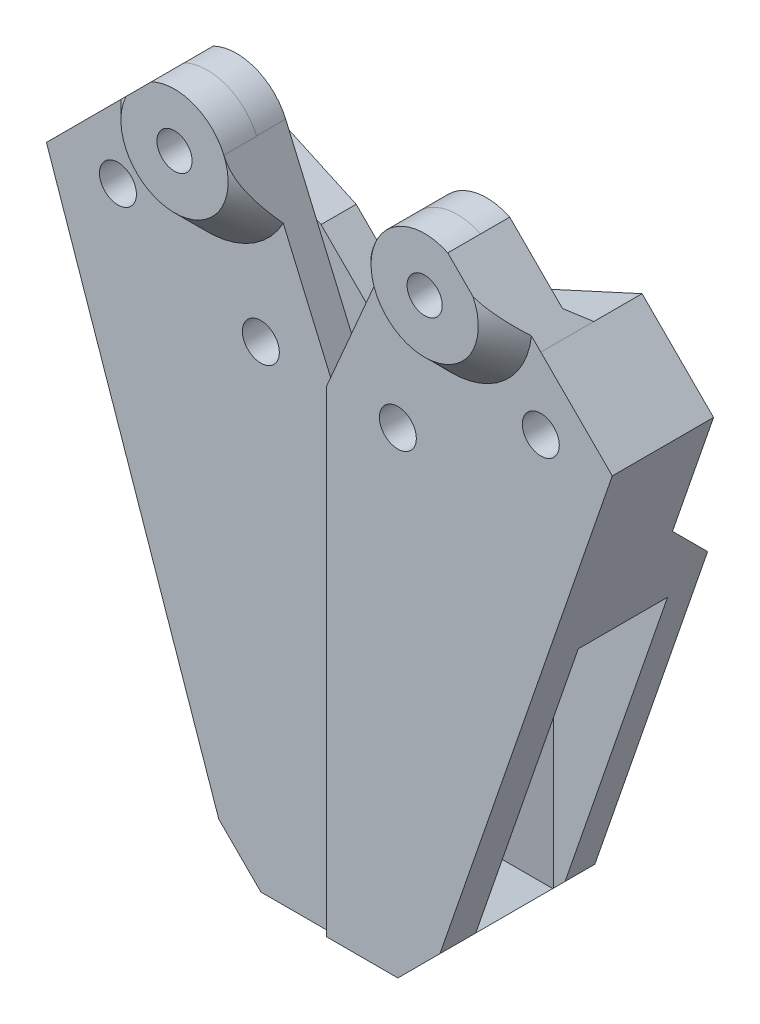
SolidWorks part; units mm, degrees
material "ABS"
ref_plane "Płaszczyzna przednia" through (0, 0, 0) normal (0, 0, 1) x (1, 0, 0)
ref_plane "Płaszczyzna górna" through (0, 0, 0) normal (0, 1, 0) x (1, 0, 0)
ref_plane "Płaszczyzna prawa" through (0, 0, 0) normal (1, 0, 0) x (0, 0, -1)
sketch "Szkic1" plane through (0, 0, 0) normal (0, 0, 1) x (1, 0, 0)
  line L0 (-24, 11) -> (-24, 23)
  line L1 (-24, 11) -> (-36, 11)
  line L2 (-24, 23) -> (-36, 11)
  line L3 (0, 0) -> (0, 12)
  line L4 (0, 12) -> (-24, 23)
  line L5 (0, 0) -> (12, 0)
  line L6 (0, 12) -> (12, 0)
  line L7 (0, 0) -> (0, -80)
  line L8 (0, -80) -> (12, -80)
  line L9 (0, -80) -> (-7.0711, -72.9289)
  line L10 (-7.0711, -72.9289) -> (-36, 11)
  line L11 (12, -80) -> (12, 0)
  circle A0 centre (0, 0) radius 3.1
  circle A1 centre (-24, 11) radius 3.1
  dimension "D1" = 6.2
  dimension "D2" = 24
  dimension "D3" = 6.2
  dimension "D4" = 11
  dimension "D5" = 12
  dimension "D6" = 12
  dimension "D7" = 12
  dimension "D8" = 12
  dimension "D9" = 80
  dimension "D10" = 12
  dimension "D11" = 135
  dimension "D12" = 10
extrude "Dodanie-wyciągnięcie1" add sketch "Szkic1" along normal blind 25 contours A1 L0 L2 L1 | A1 L1 L10 L9 L7 A0 L3 L4 L0 | A0 L5 L6 L3 | A0 L7 L8 L11 L5 region at (-28.3143, 15.3143, 0) region at (-12.4541, -19.871, 0) region at (4.3143, 4.3143, 0) region at (6.0371, -40.3066, 0)
sketch "Szkic3" plane through (12, 0, 0) normal (1, 0, 0) x (0, 0, -1)
  line L0 (-20.1, 17) -> (-20.1, -8)
  line L1 (-25, -80) -> (-25, 0) construction
  line L2 (-14.9, 17) -> (-14.9, -8)
  line L3 (-9, 17) -> (-9, -8)
  line L4 (-4, 17) -> (-4, -8)
  line L5 (0, -80) -> (0, 0) construction
  line L6 (-25, -8) -> (0, -8)
  line L7 (-25, 0) -> (0, 0) construction
  line L8 (-25, 17) -> (0, 17)
  line L9 (-25, 12) -> (-25, 0) construction
  line L10 (0, 12) -> (0, 0) construction
  line M8 (0, 0) -> (-25, 0)
  dimension "D1" = 4.9
  dimension "D2" = 10.1
  dimension "D3" = 4
  dimension "D4" = 9
  dimension "D5" = 8
  dimension "D6" = 25
extrude "Wytnij-wyciągnięcie1" cut sketch "Szkic3" against normal blind 20 contours L8 L0 L2 M8 | L0 L6 L2 M8 | L8 L3 L4 M8 | L3 L6 L4 M8 region at (12, 8.5, 17.5) region at (12, -4, 17.5) region at (12, 8.5, 6.5) region at (12, -4, 6.5)
sketch "Szkic4" plane through (12, 0, 0) normal (1, 0, 0) x (0, 0, -1)
  line L5 (-9, 12) -> (-9, 0) construction
  line L6 (-9, 4) -> (-4, 4)
  line L7 (-9, 4) -> (-9, 23)
  line L8 (-9, 23) -> (-4, 23)
  line L9 (-4, 4) -> (-4, 23)
  line L10 (-25, 23) -> (0, 23) construction
  dimension "D1" = 5
  dimension "D2" = 19
extrude "Wytnij-wyciągnięcie2" cut sketch "Szkic4" against normal blind 58
chamfer "Sfazowanie1" distance 6 angle 45 1 edges at (-8, -8, 17.5)
chamfer "Sfazowanie2" distance 12 angle 45 1 edges at (-8, 4, 6.5)
chamfer "Sfazowanie3" distance 2 angle 30 2 edges at (-8, 6.8333, 14.9) (-8, 6.8333, 20.1) first distance on face at (-8, 6.8333, 17.5)
sketch "Szkic5" plane through (0, 0, 25) normal (0, 0, 1) x (1, 0, 0)
  line L0 (-24, 23) -> (-12.8786, 34.1212)
  line L1 (-24, 23) -> (0, 12)
  line L4 (12, 0) -> (-0.7344, 29.5607)
  line L7 (12, 0) -> (0, 12)
  circle A0 centre (-9, 26) radius 2.95
  arc A5 (-0.7344, 29.5607) -> (-12.8786, 34.1212) centre (-9, 26) ccw
  line M11 (0, 12) -> (-24, 23)
  dimension "D3" = 5.9
  dimension "D1" = 26
  dimension "D2" = 9
extrude "Dodanie-wyciągnięcie2" add sketch "Szkic5" against normal blind 4.9 contours A0 M11 | A0 M11 region at (-6.0366, 21.6949, 25)
sketch "Szkic6" plane through (12, 0, 0) normal (1, 0, 0) x (0, 0, -1)
  line L1 (-9, -8) -> (0, -8)
  line L2 (-9, -8) -> (-9, 23)
  line L3 (-9, 23) -> (0, 23)
  line L4 (0, -8) -> (0, 23)
extrude "Wytnij-wyciągnięcie3" cut sketch "Szkic6" against normal blind 60
chamfer "Sfazowanie4" distance 10 angle 45 1 edges at (-8.7255, -8, 0)
sketch "Szkic8" plane through (0, 0, 25) normal (0, 0, 1) x (1, 0, 0)
  line L0 (-17.1214, 29.8785) -> (-12.8784, 34.1214)
  circle A0 centre (-9, 26) radius 2.95
  arc A1 (-17.1214, 29.8785) -> (-12.8784, 34.1214) centre (-9, 26) ccw
  dimension "D1" = 18
  dimension "D2" = 5.9
extrude "Dodanie-wyciągnięcie3" add sketch "Szkic8" along normal blind 5.5
chamfer "Sfazowanie5" distance 5.5 angle 45 1 edges at (-9.196, 17.0021, 25)
sketch "Szkic10" plane through (12, 0, 0) normal (1, 0, 0) x (0, 0, -1)
  line L0 (-20, -23) -> (-20, -75)
  line L1 (-20, -75) -> (-5, -75)
  line L2 (-5, -75) -> (-5, -23)
  line L3 (-5, -23) -> (-20, -23)
  line L4 (-25, -80) -> (0, -80) construction
  line L5 (0, -80) -> (0, -18) construction
  line L6 (-25, -80) -> (-25, 0) construction
  dimension "D1" = 5
  dimension "D2" = 5
  dimension "D3" = 5
  dimension "D4" = 5
extrude "Wytnij-wyciągnięcie6" cut sketch "Szkic10" against normal blind 70 from offset 5 offset against normal yes
chamfer "Sfazowanie9" distance 7 angle 60 4 edges at (7, -49, 20) (7, -75, 12.5) (7, -49, 5) (7, -23, 12.5) first distance on face at (7, -49, 12.5)
chamfer "Sfazowanie10" distance 3 angle 45 1 edges at (-15.4226, 19.0687, 20.1)
mirror "Lustro1" about plane through (12, 0, 25) normal (-1, 0, 0) of bodies 109
sketch "Szkic11" plane through (0, 0, 25) normal (0, 0, 1) x (1, 0, 0)
  line L0 (47.3141, 23.6858) -> (41.1214, 29.8785) construction
  line L1 (36.8784, 34.1214) -> (41.1214, 29.8785) construction
  line L2 (24.7174, 29.5212) -> (20.2365, 19.1195) construction
  line L3 (47.3141, 23.6858) -> (41.1214, 29.8785)
  line L4 (36.8784, 34.1214) -> (41.1214, 29.8785)
  line L5 (24.7174, 29.5212) -> (20.2365, 19.1195)
  line L7 (20.2365, 19.1195) -> (12, 0)
  line L8 (12, 0) -> (12, -80)
  line L9 (12, -80) -> (24, -80)
  line L10 (24, -80) -> (31.0711, -72.9289)
  line L11 (31.0711, -72.9289) -> (60, 11)
  line L12 (60, 11) -> (48, 23)
  line L13 (48, 23) -> (47.3141, 23.6858)
  line L14 (20.2365, 19.1195) -> (12, 0)
  line L15 (12, 0) -> (12, -80)
  line L16 (12, -80) -> (24, -80)
  line L17 (24, -80) -> (31.0711, -72.9289)
  line L18 (31.0711, -72.9289) -> (60, 11)
  line L19 (60, 11) -> (48, 23)
  line L20 (48, 23) -> (47.3141, 23.6858)
  arc A0 (36.8784, 34.1214) -> (24.7174, 29.5212) centre (33, 26) ccw construction
  arc A1 (20.2365, 19.1195) -> (47.3141, 23.6858) centre (33, 26) ccw
  arc A3 (36.8784, 34.1214) -> (24.7174, 29.5212) centre (33, 26) ccw
  circle A4 centre (48, 11) radius 3.1 construction
  circle A5 centre (24, 0) radius 3.1 construction
  circle A6 centre (48, 11) radius 3.1
  circle A7 centre (24, 0) radius 3.1
  circle A8 centre (33, 26) radius 2.95 construction
  circle A9 centre (33, 26) radius 2.95
  dimension "D1" = 0
extrude "Dodanie-wyciągnięcie4" add sketch "Szkic11" along normal blind 1
sketch "Szkic12" plane through (0, 0, 20.1) normal (0, 0, -1) x (-1, 0, 0)
  circle A0 centre (-33, 26) radius 2.95 construction
  circle A1 centre (-33, 26) radius 2.95
  circle A2 centre (-33, 26) radius 4.5
  dimension "D1" = 9
extrude "Dodanie-wyciągnięcie5" add sketch "Szkic12" along normal blind 0.8
chamfer "Sfazowanie11" distance 0.8 angle 45 1 edges at (33, 21.5, 20.1)
